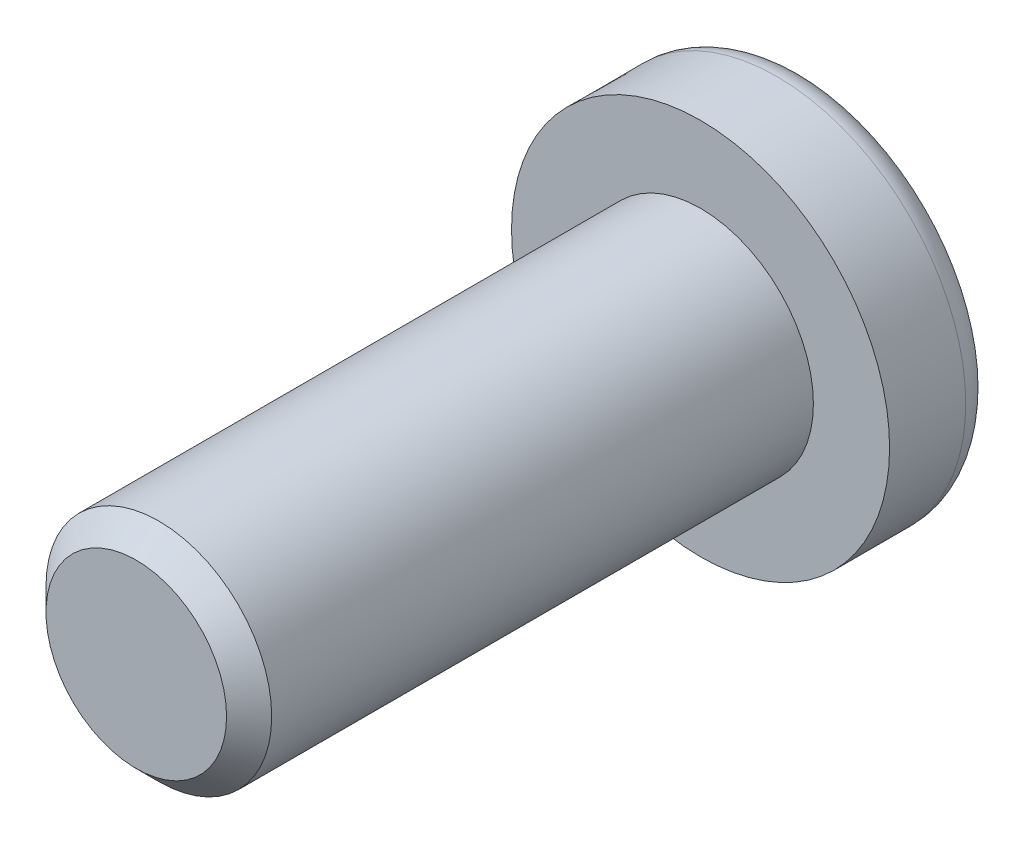
SolidWorks part; units mm, degrees
ref_plane "Plan1" through (0, 0, 0) normal (0, 0, 1) x (1, 0, 0)
ref_plane "Plan2" through (0, 0, 0) normal (0, 1, 0) x (1, 0, 0)
ref_plane "Plan3" through (0, 0, 0) normal (1, 0, 0) x (0, 0, -1)
ref_axis "Z Axis" through (0, 0, -50) along (0, 0, 1)
sketch "Esquisse1" plane through (0, 0, 0) normal (0, 1, 0) x (1, 0, 0)
  line L0 (0, 0) -> (0, 3.1) construction
  line L1 (0, 0) -> (3.35, 0)
  line L2 (0, 0) -> (0, 2.5036)
  line L3 (0, 0) -> (0, 3.1) construction
  line L5 (3.35, 0) -> (3.35, 3.1) construction
  line L6 (3.35, 1.35) -> (3.35, 0)
  arc A1 (3.2108, 1.7062) -> (3.35, 1.35) centre (2.8333, 1.3534) cw
  arc A2 (3.2108, 1.7062) -> (0, 2.5036) centre (-0.1126, -4.8127) ccw
  point P9 (3.35, 1.55)
  dimension "D3" = 3.35
  dimension "D1" = 0.5167
  dimension "D2" = 3.1
revolve "Base-Révolution" add sketch "Esquisse1" angle 360 about L0 reverse direction yes
ref_plane "Plan4" through (0, 0, -3.1) normal (0, 0, 1) x (1, 0, 0)
sketch "Esquisse2" plane through (0, 0, -3.1) normal (0, 0, 1) x (1, 0, 0)
  line L0 (0.6, -0.6) -> (0.6, -2.35)
  line L1 (-2.35, 0.6) -> (-0.6, 0.6)
  line L2 (-2.35, 0.6) -> (-2.35, -0.6)
  line L3 (-2.35, -0.6) -> (-0.6, -0.6)
  line L4 (2.35, 0.6) -> (2.35, -0.6)
  line L5 (-0.6, 2.35) -> (0.6, 2.35)
  line L6 (-0.6, 2.35) -> (-0.6, 0.6)
  line L7 (-0.6, -2.35) -> (0.6, -2.35)
  line L8 (0.6, 2.35) -> (0.6, 0.6)
  line L9 (0.6, 0.6) -> (2.35, 0.6)
  line L10 (-0.6, -0.6) -> (-0.6, -2.35)
  line L11 (0.6, -0.6) -> (2.35, -0.6)
  dimension "D2" = 4.7
  dimension "D3" = 2.35
  dimension "D4" = 2.35
  dimension "D5" = 4.7
extrude "Enlev. mat.-Extru.1" cut sketch "Esquisse2" along normal blind 1
sketch "Esquisse3" plane through (0, 0, 0) normal (0, 1, 0) x (1, 0, 0)
  line L1 (0, 0) -> (0, -10) construction
  line L2 (0, 0) -> (2, 0)
  line L3 (0, 0) -> (0, -10)
  line L4 (0, -10) -> (2, -10)
  line L6 (2, 0) -> (2, -10)
  dimension "D1" = 10
  dimension "D2" = 2
revolve "Boss.-Révol.1" add sketch "Esquisse3" angle 360 about L1 reverse direction yes
sketch "Esquisse4" plane through (0, 0, 0) normal (0, 1, 0) x (1, 0, 0)
  line L0 (1.3, -10.0488) -> (1.3, -9.9512)
  line L2 (1.3, -9.9512) -> (2.07, -9.5066)
  line L3 (1.3, -10.0488) -> (2.07, -10.4934)
  line L4 (2.07, -9.5066) -> (2.07, -10.4934)
  line L6 (-2, -10) -> (2, -10) construction
  point P4 (2, -10)
  dimension "D2" = 0.0488
  dimension "D3" = 0.0488
  dimension "D4" = 0.77
  dimension "D5" = 60
  dimension "D1" = 0.7
  dimension "D6" = 60
chamfer "Chanfrein1" distance 0.4 angle 45 1 edges at (2, 0, 10)
sketch "Esquisse5" plane through (0, 0, 10) normal (0, 0, 1) x (1, 0, 0)
  circle A0 centre (0, 0) radius 2 construction
  circle A1 centre (0, 0) radius 2
curve "Hélice1" pitch 1 height 10 turns 10
sweep "Enlèvement de matière-Balayage1" [suppressed] cut profiles "Esquisse4" path "Hélice1"
sketch "Esquisse6" plane through (0, 0, -2.1) normal (0, 0, -1) x (-1, 0, 0)
  line L10 (2.2064, 0.6) -> (0.6, 0.6)
  line L11 (2.2064, 0.6) -> (0.6, 0.6)
  line L14 (0.6, 0.6) -> (0.6, 2.2064)
  line L15 (-0.6, 2.2064) -> (-0.6, 0.6)
  line L16 (-0.6, 2.2064) -> (-0.6, 0.6)
  line L17 (-0.6, 0.6) -> (-2.2064, 0.6)
  line L20 (-0.6, -0.6) -> (-0.6, -2.2064)
  line L23 (0.6, -0.6) -> (2.2064, -0.6)
  line L26 (0.6, 0.6) -> (0.6, 2.2064)
  line L27 (-2.2064, -0.6) -> (-0.6, -0.6)
  line L28 (-2.2064, -0.6) -> (-0.6, -0.6)
  line L29 (-0.6, 0.6) -> (-2.2064, 0.6)
  line L32 (-0.6, -0.6) -> (-0.6, -2.2064)
  line L33 (0.6, -2.2064) -> (0.6, -0.6)
  line L34 (0.6, -2.2064) -> (0.6, -0.6)
  line L35 (0.6, -0.6) -> (2.2064, -0.6)
  arc A1 (-2.2064, 0.6) -> (-2.2064, -0.6) centre (0, 0) ccw
  arc A2 (-2.2064, 0.6) -> (-2.2064, -0.6) centre (0, 0) ccw
  arc A6 (-0.6, -2.2064) -> (0.6, -2.2064) centre (0, 0) ccw
  arc A7 (-0.6, -2.2064) -> (0.6, -2.2064) centre (0, 0) ccw
  arc A8 (2.2064, -0.6) -> (2.2064, 0.6) centre (0, 0) ccw
  arc A9 (2.2064, -0.6) -> (2.2064, 0.6) centre (0, 0) ccw
  arc A10 (0.6, 2.2064) -> (-0.6, 2.2064) centre (0, 0) ccw
  arc A11 (0.6, 2.2064) -> (-0.6, 2.2064) centre (0, 0) ccw
  dimension "D1" = 0
extrude "Enlèv. mat.-Extru.1" cut sketch "Esquisse6" against normal blind 1
equation "\"D1@Chanfrein1\"=\"D2@Esquisse3\"*0.2"
equation "\"D4@Esquisse4\"=1.1*\"D1@Esquisse4\""
equation "\"D1@Plan4\"=\"D2@Esquisse1\""
equation "\"D1@Esquisse1\"=\"D2@Esquisse1\"/6"
